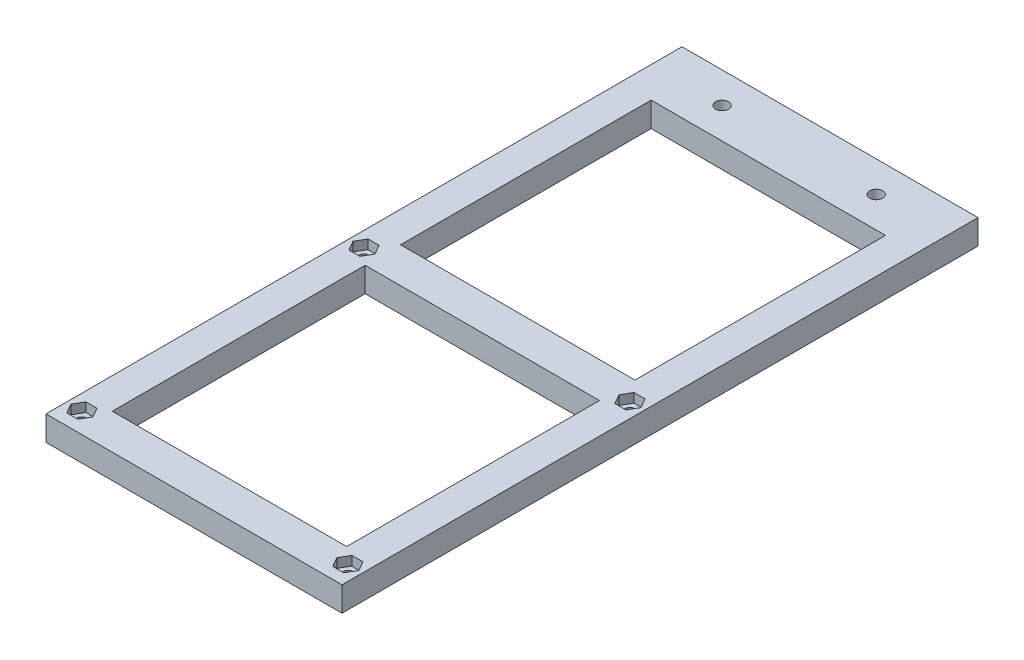
SolidWorks part; units mm, degrees
note: The reader was unsure of these and kept them because the rebuilt part matched: shared geometry of "Эскиз1<11>", "Эскиз1<12>".
ref_plane "Спереди" through (0, 0, 0) normal (0, 0, 1) x (1, 0, 0)
ref_plane "Сверху" through (0, 0, 0) normal (0, 1, 0) x (1, 0, 0)
ref_plane "Справа" through (0, 0, 0) normal (1, 0, 0) x (0, 0, -1)
sketch "Эскиз1" plane through (0, 0, 0) normal (0, 1, 0) x (1, 0, 0)
  line L1 (38, -41) -> (-38, -41)
  line L2 (38, -41) -> (38, 41)
  line L3 (38, 41) -> (-38, 41)
  line L4 (-38, -41) -> (-38, 41)
  line L5 (0, 41) -> (0, -41) construction
  line L6 (38, 0) -> (-38, 0) construction
  line L7 (48, -52.5) -> (-48, -52.5)
  line L8 (48, -52.5) -> (48, 52.5)
  line L9 (48, 52.5) -> (-48, 52.5)
  line L10 (-48, -52.5) -> (-48, 52.5)
  line L11 (0, 52.5) -> (0, -52.5) construction
  line L12 (48, 0) -> (-48, 0) construction
  line L13 (43.125, -45.75) -> (-43.125, -45.75) construction
  line L14 (43.125, -45.75) -> (43.125, 45.75) construction
  line L15 (43.125, 45.75) -> (-43.125, 45.75) construction
  line L16 (-43.125, -45.75) -> (-43.125, 45.75) construction
  line L17 (0, 45.75) -> (0, -45.75) construction
  line L18 (43.125, 0) -> (-43.125, 0) construction
  line L19 (25, -143.75) -> (-25, -143.75) construction
  line L20 (25, -143.75) -> (25, 143.75) construction
  line L21 (25, 143.75) -> (-25, 143.75) construction
  line L22 (-25, -143.75) -> (-25, 143.75) construction
  line L23 (0, 143.75) -> (0, -143.75) construction
  line L24 (25, 0) -> (-25, 0) construction
  line L25 (-48, 52.5) -> (48, 52.5)
  line L26 (-48, 52.5) -> (-48, 153.75)
  line L27 (-48, 153.75) -> (48, 153.75)
  line L28 (48, 52.5) -> (48, 153.75)
  line L29 (-38, 52.5) -> (38, 52.5)
  line L30 (-38, 52.5) -> (-38, 133.75)
  line L31 (-38, 133.75) -> (38, 133.75)
  line L32 (38, 52.5) -> (38, 133.75)
  circle A0 centre (-43.125, 45.75) radius 1.75
  circle A1 centre (43.125, 45.75) radius 1.75
  circle A2 centre (43.125, -45.75) radius 1.75
  circle A3 centre (-43.125, -45.75) radius 1.75
  circle A4 centre (-25, 143.75) radius 2.1
  circle A5 centre (25, 143.75) radius 2.1
  point P0 (0, 0)
  point P4 (0, 0)
  point P11 (0, 0)
  point P25 (0, 0)
  dimension "D7" = 3.5
  dimension "D11" = 4.2
  dimension "D1" = 82
  dimension "D2" = 76
  dimension "D3" = 105
  dimension "D4" = 96
  dimension "D5" = 91.5
  dimension "D6" = 86.25
  dimension "D8" = 4.875
  dimension "D9" = 98
  dimension "D10" = 10
  dimension "D12" = 10
extrude "Бобышка-Вытянуть1" add sketch "Эскиз1" along normal blind 8 contours L2 L3 L4 L1 | L9 L10 L7 L8 | A2 | A1 | A0 | A3
extrude "Бобышка-Вытянуть5" add sketch "Эскиз1<11>" along normal blind 8 contours L26 L27 L28 L25 | A5 | A4 | L31 L32 L29 L30
sketch "Эскиз1<11>" plane through (0, 0, 0) normal (0, 1, 0) x (1, 0, 0) same geometry as "Эскиз1"
extrude "Вырез-Вытянуть4" cut sketch "Эскиз1<12>" against normal through all and the other way through all contours L30 L31 L32 L29
sketch "Эскиз1<12>" plane through (0, 0, 0) normal (0, 1, 0) x (1, 0, 0) same geometry as "Эскиз1"
sketch "Эскиз3" plane through (0, 0, 0) normal (0, -1, 0) x (1, 0, 0)
  circle A0 centre (-25, -143.75) radius 2.1 construction
  circle A1 centre (25, -143.75) radius 2.1 construction
  circle A2 centre (-25, -143.75) radius 2.1
  circle A3 centre (25, -143.75) radius 2.1
  circle A4 centre (-25, -143.75) radius 6.1
  circle A5 centre (25, -143.75) radius 6.1
  dimension "D2" = 12.2
  dimension "D1" = 4
extrude "Вырез-Вытянуть5" cut sketch "Эскиз3" against normal blind 4 contours A5 | A4
sketch "Эскиз4" plane through (0, 8, 0) normal (0, 1, 0) x (1, 0, 0)
  line L1 (38, 41) -> (-38, 41) construction
  line L2 (-39.5454, 45.75) -> (-41.3352, 48.85)
  line L3 (-41.3352, 48.85) -> (-44.9148, 48.85)
  line L4 (-44.9148, 48.85) -> (-46.7046, 45.75)
  line L5 (-46.7046, 45.75) -> (-44.9148, 42.65)
  line L6 (-44.9148, 42.65) -> (-41.3352, 42.65)
  line L7 (-41.3352, 42.65) -> (-39.5454, 45.75)
  line L8 (39.5454, 45.75) -> (41.3352, 42.65)
  line L9 (41.3352, 42.65) -> (44.9148, 42.65)
  line L10 (44.9148, 42.65) -> (46.7046, 45.75)
  line L11 (46.7046, 45.75) -> (44.9148, 48.85)
  line L12 (44.9148, 48.85) -> (41.3352, 48.85)
  line L13 (41.3352, 48.85) -> (39.5454, 45.75)
  line L14 (39.5454, -45.75) -> (41.3352, -48.85)
  line L15 (41.3352, -48.85) -> (44.9148, -48.85)
  line L16 (44.9148, -48.85) -> (46.7046, -45.75)
  line L17 (46.7046, -45.75) -> (44.9148, -42.65)
  line L18 (44.9148, -42.65) -> (41.3352, -42.65)
  line L19 (41.3352, -42.65) -> (39.5454, -45.75)
  line L20 (-39.5454, -45.75) -> (-41.3352, -42.65)
  line L21 (-41.3352, -42.65) -> (-44.9148, -42.65)
  line L22 (-44.9148, -42.65) -> (-46.7046, -45.75)
  line L23 (-46.7046, -45.75) -> (-44.9148, -48.85)
  line L24 (-44.9148, -48.85) -> (-41.3352, -48.85)
  line L25 (-41.3352, -48.85) -> (-39.5454, -45.75)
  line L26 (48, -52.5) -> (-48, -52.5) construction
  circle A0 centre (43.125, 45.75) radius 3.1 construction
  circle A1 centre (43.125, -45.75) radius 3.1 construction
  circle A2 centre (-43.125, -45.75) radius 3.1 construction
  circle A3 centre (-43.125, 45.75) radius 3.1 construction
  dimension "D1" = 6.2
extrude "Вырез-Вытянуть6" cut sketch "Эскиз4" against normal blind 3
